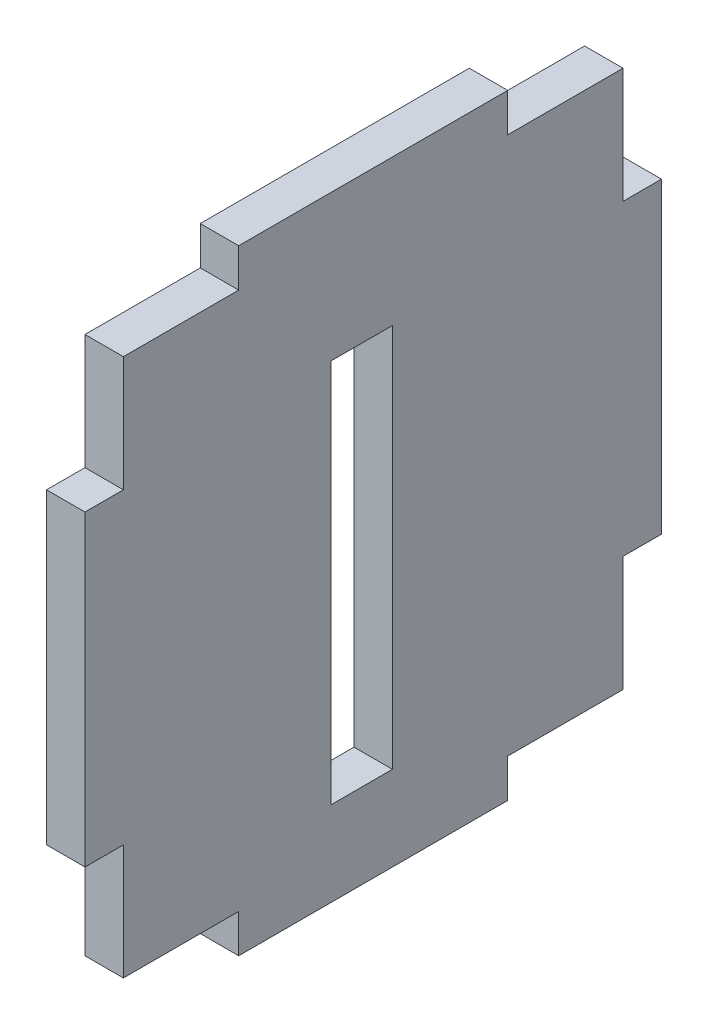
SolidWorks part; units mm, degrees
material "Acrylic (Medium-high impact)"
ref_plane "Front Plane" through (0, 0, 0) normal (0, 0, 1) x (1, 0, 0)
ref_plane "Top Plane" through (0, 0, 0) normal (0, 1, 0) x (1, 0, 0)
ref_plane "Right Plane" through (0, 0, 0) normal (1, 0, 0) x (0, 0, -1)
sketch "Sketch1" plane through (0, 0, 0) normal (1, 0, 0) x (0, 0, -1)
  line L1 (-37.5, -40) -> (37.5, -40)
  line L2 (-37.5, -40) -> (-37.5, 40)
  line L3 (-37.5, 40) -> (37.5, 40)
  line L4 (37.5, -40) -> (37.5, 40)
  line L5 (-37.5, -40) -> (37.5, 40) construction
  line L6 (-37.5, 40) -> (37.5, -40) construction
  point P0 (0, 0)
  dimension "D1" = 75
  dimension "D2" = 80
extrude "Boss-Extrude1" add sketch "Sketch1" along normal blind 5
sketch "Sketch3" plane through (5, 0, 0) normal (1, 0, 0) x (0, 0, -1)
  line L0 (-37.5, 20) -> (-32.5, 20)
  line L1 (-37.5, 40) -> (-37.5, -40) construction
  line L2 (-32.5, 20) -> (-32.5, 35)
  line L3 (-32.5, 35) -> (-17.5, 35)
  line L4 (-17.5, 35) -> (-17.5, 40)
  line L5 (37.5, 40) -> (-37.5, 40) construction
  line L6 (-17.5, 40) -> (-37.5, 40)
  line L7 (-37.5, 40) -> (-37.5, 20)
  dimension "D1" = 20
  dimension "D2" = 5
extrude "Cut-Extrude1" cut sketch "Sketch3" against normal through all both and the other way through all
mirror "Mirror1" about plane through (0, 0, 0) normal (0, 0, 1) of "Cut-Extrude1" second plane through (0, 0, 0) second plane normal (0, 1, 0)
sketch "Sketch4" plane through (5, 0, 0) normal (1, 0, 0) x (0, 0, -1)
  line L0 (37.5, -20) -> (37.5, 20) construction
  line L1 (-5.5, -28.9881) -> (2.5, -28.9881)
  line L2 (-5.5, -28.9881) -> (-5.5, 21.0119)
  line L3 (-5.5, 21.0119) -> (2.5, 21.0119)
  line L4 (2.5, -28.9881) -> (2.5, 21.0119)
  dimension "D1" = 8
  dimension "D2" = 50
  dimension "D3" = 35
extrude "Cut-Extrude2" cut sketch "Sketch4" against normal through all both
